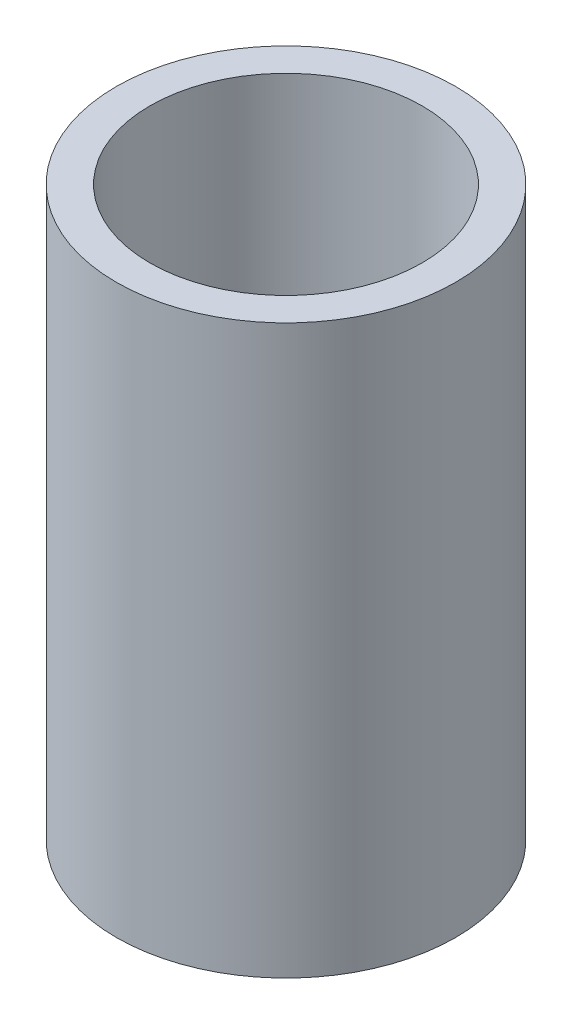
SolidWorks part; units mm, degrees
ref_plane "Front Plane" through (0, 0, 0) normal (0, 0, 1) x (1, 0, 0)
ref_plane "Top Plane" through (0, 0, 0) normal (0, 1, 0) x (1, 0, 0)
ref_plane "Right Plane" through (0, 0, 0) normal (1, 0, 0) x (0, 0, -1)
sketch "Sketch1" plane through (0, 0, 0) normal (0, 1, 0) x (1, 0, 0)
  circle A0 centre (0, 0) radius 17.5
  dimension "SLEEVE_OD" = 35
extrude "Boss-Extrude1" add sketch "Sketch1" along normal blind 58.5399
sketch "Sketch2" plane through (0, 0, 0) normal (0, 1, 0) x (1, 0, 0)
  circle A0 centre (0, 0) radius 14.04
  dimension "BORE_D" = 28.0799
extrude "Cut-Extrude1" cut sketch "Sketch2" along normal through all
chamfer "Chamfer1" distance 2.2946 angle 34.602 rebuild error yes
